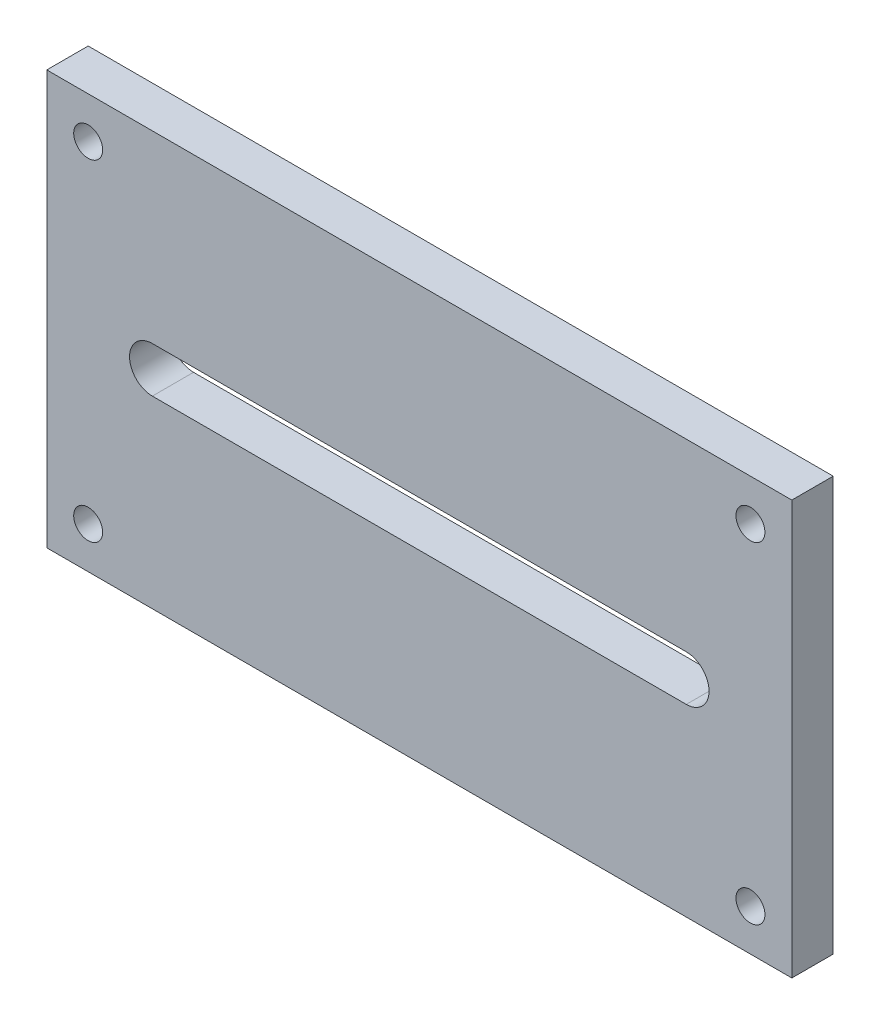
SolidWorks part; units mm, degrees
ref_plane "Front Plane" through (0, 0, 0) normal (0, 0, 1) x (1, 0, 0)
ref_plane "Top Plane" through (0, 0, 0) normal (0, 1, 0) x (1, 0, 0)
ref_plane "Right Plane" through (0, 0, 0) normal (1, 0, 0) x (0, 0, -1)
sketch "Sketch1" plane through (0, 0, 0) normal (0, 0, 1) x (1, 0, 0)
  line L1 (-45, 25) -> (45, 25)
  line L2 (-45, 25) -> (-45, -25)
  line L3 (-45, -25) -> (45, -25)
  line L4 (45, 25) -> (45, -25)
  line L5 (-45, 25) -> (45, -25) construction
  line L6 (-45, -25) -> (45, 25) construction
  point P0 (0, 0)
  dimension "D1" = 50
  dimension "D2" = 90
extrude "Boss-Extrude1" add sketch "Sketch1" along normal blind 5
hole_wizard "Ø5.5 (5.5) Diameter Slot1" positions "Sketch2" profile "Sketch3" size "Ø5.5" standard "ISO" slot yes end condition through all
sketch "Sketch2" plane through (0, 0, 0) normal (0, 0, -1) x (-1, 0, 0)
  line L0 (35, 0) -> (-35, 0) construction
  point P0 (0, 0)
  point P7 (0, 0)
  point P8 (0, 0)
  dimension "D1" = 70
sketch "Sketch3" plane through (0, 0, 0) normal (1, 0, 0) x (0, 1, 0)
  line L0 (0, 0) -> (0, 5)
  line L1 (0, 5) -> (2.75, 5)
  line L2 (2.75, 5) -> (2.75, 0.025)
  line L3 (2.75, 0.025) -> (2.775, 0)
  line L5 (2.775, 0) -> (0, 0)
  line L6 (-2.75, 0.025) -> (-2.775, 0) construction
  line L11 (0, -6.35) -> (0, 107.95) construction
  dimension "Thru Hole Dia." = 5.5
  dimension "Thru Hole Depth" = 5
  dimension "Near C'Sink Dia." = 5.55
  dimension "Near C'Sink Angle" = 90
hole_wizard "Ø3.5 (3.5) Diameter Hole1" positions "Sketch4" profile "Sketch5" hole size "Ø3.5" standard "ISO" end condition through all
sketch "Sketch4" plane through (0, 0, 0) normal (0, 0, -1) x (-1, 0, 0)
  line L0 (-45, 25) -> (-45, -25) construction
  line L1 (45, 25) -> (-45, 25) construction
  line L2 (45, -25) -> (-45, -25) construction
  line L3 (45, 25) -> (45, -25) construction
  point P0 (-40, 20)
  point P2 (40, 20)
  point P4 (40, -20)
  point P6 (-40, -20)
  point P9 (-38.7805, 19.1328)
  point P10 (0, 0)
  point P11 (0, 0)
  point P12 (0, 0)
  point P15 (0, 0)
  dimension "D1" = 5
  dimension "D2" = 5
  dimension "D3" = 5
  dimension "D4" = 5
sketch "Sketch5" plane through (40, 20, 0) normal (1, 0, 0) x (0, 1, 0)
  line L0 (0, 0) -> (0, 5)
  line L1 (0, 5) -> (1.75, 5)
  line L2 (1.75, 5) -> (1.75, 0.025)
  line L3 (1.75, 0.025) -> (1.775, 0)
  line L5 (1.775, 0) -> (0, 0)
  line L6 (-1.75, 0.025) -> (-1.775, 0) construction
  line L11 (0, -6.35) -> (0, 107.95) construction
  dimension "Thru Hole Dia." = 3.5
  dimension "Thru Hole Depth" = 5
  dimension "Near C'Sink Dia." = 3.55
  dimension "Near C'Sink Angle" = 90
